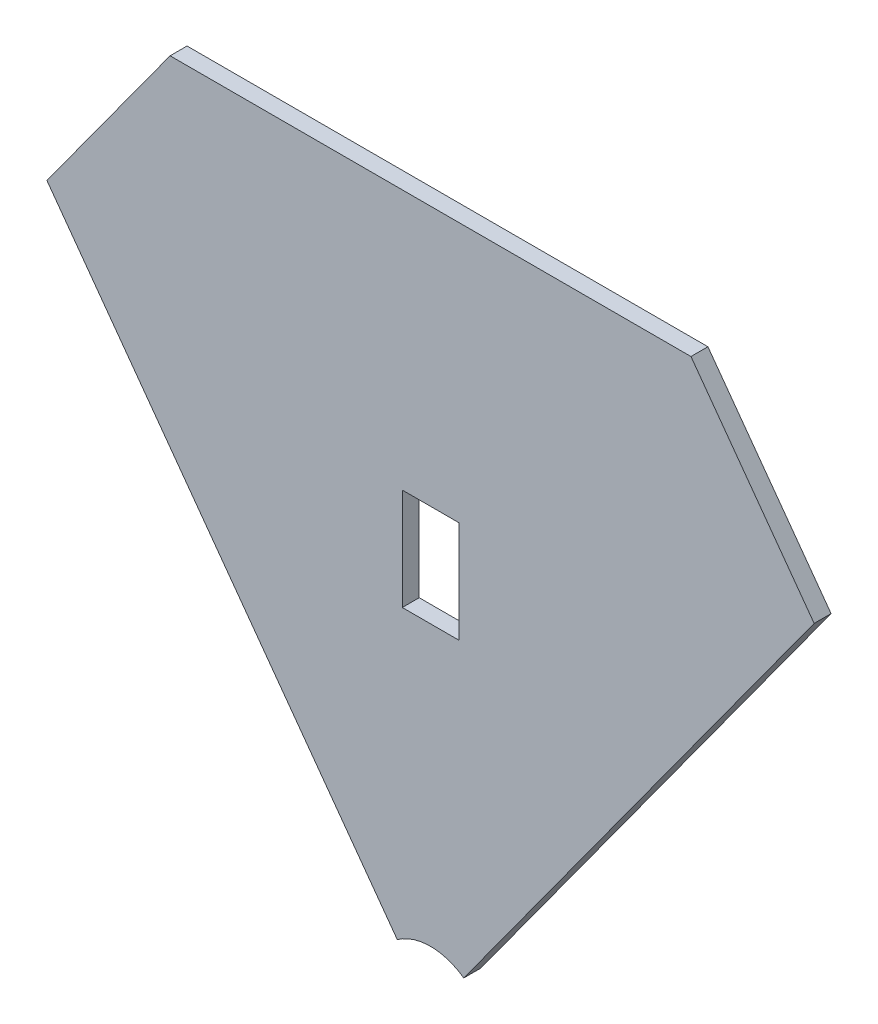
SolidWorks part; units mm, degrees
ref_plane "Front Plane" through (0, 0, 0) normal (0, 0, 1) x (1, 0, 0)
ref_plane "Top Plane" through (0, 0, 0) normal (0, 1, 0) x (1, 0, 0)
ref_plane "Right Plane" through (0, 0, 0) normal (1, 0, 0) x (0, 0, -1)
sketch "Sketch3" plane through (0, 0, 0) normal (0, 0, 1) x (1, 0, 0)
  line L0 (0, 0) -> (56.9791, 78.425)
  line L1 (56.9791, 78.425) -> (-56.9791, 78.425)
  line L2 (-56.9791, 78.425) -> (0, 0)
  line L4 (-5, 77.425) -> (5, 77.425)
  line L5 (-5, 77.425) -> (-5, 59.425)
  line L6 (-5, 59.425) -> (5, 59.425)
  line L7 (5, 77.425) -> (5, 59.425)
  point P5 (0, 78.425)
  point P9 (5, 68.425)
  point P10 (0, 59.425)
  dimension "D1" = 72
  dimension "D2" = 78.425
  dimension "D3" = 10
  dimension "D4" = 18
  dimension "D5" = 10
extrude "Boss-Extrude1" add sketch "Sketch3" along normal blind 3
ref_plane "Offset_R" through (0, 78.425, 0) normal (0, 1, 0) x (1, 0, 0)
sketch "Sketch4" plane through (0, 0, 0) normal (0, 0, -1) x (-1, 0, 0)
  line L0 (-56.9791, 78.425) -> (-89.6735, 123.425)
  line L1 (-89.6735, 123.425) -> (89.6735, 123.425)
  line L2 (89.6735, 123.425) -> (56.9791, 78.425)
  line L3 (56.9791, 78.425) -> (-56.9791, 78.425)
  line L4 (0, 0) -> (-56.9791, 78.425) construction
  line L5 (56.9791, 78.425) -> (0, 0) construction
  dimension "D1" = 45
extrude "Boss-Extrude2" add sketch "Sketch4" against normal up to surface (3 mm away) up to face at (0, 52.2833, 3)
sketch "Sketch5" plane through (0, 0, 3) normal (0, 0, 1) x (1, 0, 0)
  line L0 (-89.6735, 123.425) -> (-46.081, 123.425)
  line L1 (-89.6735, 123.425) -> (89.6735, 123.425) construction
  line L2 (-46.081, 123.425) -> (-67.8772, 93.425)
  line L3 (-89.6735, 123.425) -> (0, 0) construction
  line L4 (-67.8772, 93.425) -> (-89.6735, 123.425)
  line L5 (89.6735, 123.425) -> (46.081, 123.425)
  line L6 (46.081, 123.425) -> (67.8772, 93.425)
  line L7 (0, 0) -> (89.6735, 123.425) construction
  line L8 (67.8772, 93.425) -> (89.6735, 123.425)
  dimension "D1" = 30
extrude "Cut-Extrude1" cut sketch "Sketch5" against normal through all
ref_axis "Axis1" through (0, 0, 10.9079) along (0, 0, -1)
sketch "Sketch6" plane through (0, 0, 0) normal (0, 0, -1) x (-1, 0, 0)
  circle A0 centre (0, 0) radius 10
extrude "Cut-Extrude2" cut sketch "Sketch6" against normal through all
